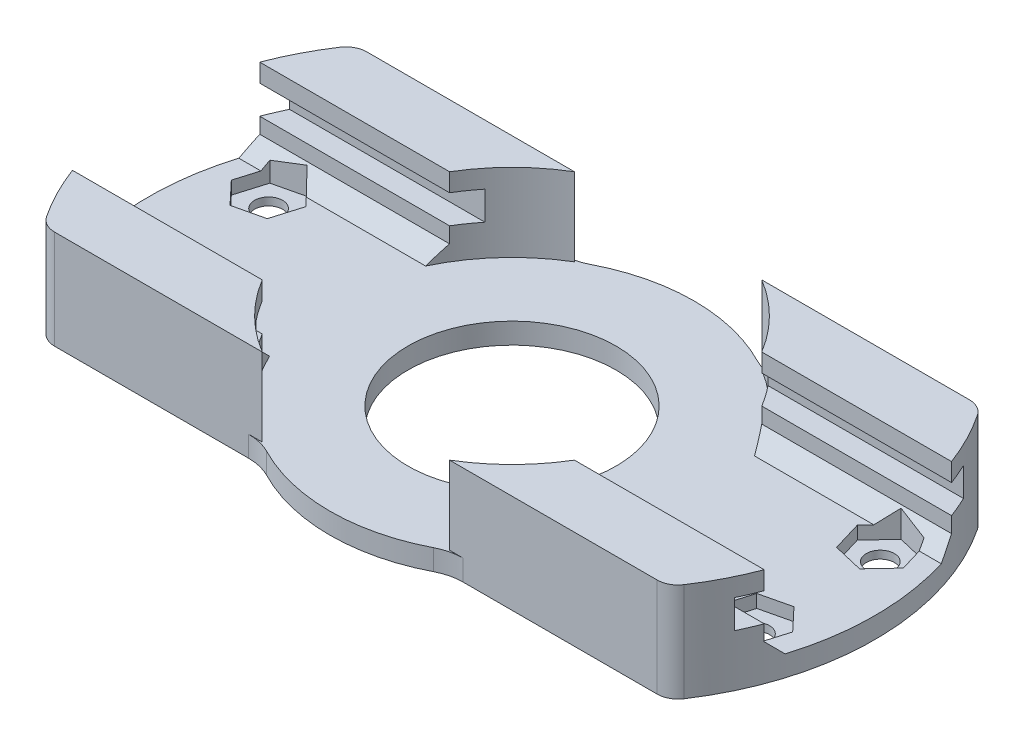
SolidWorks part; units mm, degrees
ref_plane "Спереди" through (0, 0, 0) normal (0, 0, 1) x (1, 0, 0)
ref_plane "Сверху" through (0, 0, 0) normal (0, 1, 0) x (1, 0, 0)
ref_plane "Справа" through (0, 0, 0) normal (1, 0, 0) x (0, 0, -1)
sketch "Эскиз1" plane through (0, 0, 0) normal (0, 1, 0) x (1, 0, 0)
  line L0 (-2.3838, 26) -> (62.3838, 26)
  line L1 (0, 0) -> (60, 0)
  line L2 (0, 0) -> (0, 30) construction
  line L3 (0, 30) -> (60, 30)
  line L4 (60, 0) -> (60, 30) construction
  line L5 (-4.8784, 15) -> (64.8784, 15) construction
  line L6 (-3.2374, 24) -> (63.2374, 24)
  line L7 (-2.3838, 4) -> (62.3838, 4)
  line L8 (-3.2374, 6) -> (63.2374, 6)
  line L9 (15, 0) -> (15, 6)
  line L10 (15, 30) -> (15, 24)
  line L11 (30, 30) -> (30, 0) construction
  line L12 (45, 0) -> (45, 6)
  line L13 (45, 30) -> (45, 24)
  arc A0 (0, 30) -> (0, 0) centre (20.6216, 15) ccw
  arc A1 (60, 30) -> (60, 0) centre (39.3784, 15) cw
  circle A2 centre (30, 15) radius 17.4929
  dimension "D3" = 25.5
  dimension "D1" = 60
  dimension "D2" = 30
  dimension "D4" = 4
  dimension "D5" = 2
  dimension "D6" = 15
extrude "Бобышка-Вытянуть1" add sketch "Эскиз1" along normal blind 2 contours A1 L1 A0 L3
extrude "Бобышка-Вытянуть2" add sketch "Эскиз1<3>" along normal blind 3 from surface contours L3 A0 L0 L10 | L0 A0 L6 L10 | L7 A0 L1 L9 | L8 A0 L7 L9 | A1 L3 L13 L0 | A1 L0 L13 L6 | A1 L8 L12 L7 | A1 L7 L12 L1 | A2 L1 L12 L7 | A2 L7 L12 | A2 L13 L0 | A2 L0 L13 L3 | A2 L0 L10 | A2 L3 L10 L0 | A2 L7 L9 L1 | A2 L9 L7 region at (6.8482, 0, -27.9513) region at (6.0846, 0, -24.992) region at (16.9656, 0, -28.4412) region at (15.4547, 0, -25.3502) region at (6.0846, 0, -5.008) region at (43.0344, 0, -28.4412) region at (44.5453, 0, -25.3502) region at (53.9154, 0, -24.992) region at (15.4547, 0, -4.6498) region at (6.8482, 0, -2.0487) region at (53.1518, 0, -27.9513) region at (53.9154, 0, -5.008) region at (44.5453, 0, -4.6498) region at (16.9656, 0, -1.5588) region at (43.0344, 0, -1.5588) region at (53.1518, 0, -2.0487) starting at face at (30, 2, -15)
sketch "Эскиз1<3>" plane through (0, 0, 0) normal (0, 1, 0) x (1, 0, 0) same geometry as "Эскиз1"
extrude "Бобышка-Вытянуть3" add sketch "Эскиз1<4>" along normal blind 2.75 from surface contours A1 L3 L13 L0 | A1 L7 L12 L1 | L7 A0 L1 L9 | L3 A0 L0 L10 | A2 L1 L12 L7 | A2 L7 L9 L1 | A2 L3 L10 L0 | A2 L0 L13 L3 region at (6.8482, 0, -27.9513) region at (16.9656, 0, -28.4412) region at (43.0344, 0, -28.4412) region at (6.8482, 0, -2.0487) region at (53.1518, 0, -27.9513) region at (16.9656, 0, -1.5588) region at (43.0344, 0, -1.5588) region at (53.1518, 0, -2.0487) starting at face at (8.048, 5, -27.1195)
sketch "Эскиз1<4>" plane through (0, 0, 0) normal (0, 1, 0) x (1, 0, 0) same geometry as "Эскиз1"
extrude "Бобышка-Вытянуть4" add sketch "Эскиз1<5>" along normal blind 1.75 from surface contours L3 A0 L0 L10 | L0 A0 L6 L10 | L8 A0 L7 L9 | L7 A0 L1 L9 | A1 L7 L12 L1 | A1 L8 L12 L7 | A1 L3 L13 L0 | A1 L0 L13 L6 | A2 L13 L0 | A2 L0 L13 L3 | A2 L1 L12 L7 | A2 L7 L12 | A2 L7 L9 L1 | A2 L9 L7 | A2 L3 L10 L0 | A2 L0 L10 region at (6.8482, 0, -27.9513) region at (6.0846, 0, -24.992) region at (16.9656, 0, -28.4412) region at (15.4547, 0, -25.3502) region at (6.0846, 0, -5.008) region at (43.0344, 0, -28.4412) region at (44.5453, 0, -25.3502) region at (53.9154, 0, -24.992) region at (15.4547, 0, -4.6498) region at (6.8482, 0, -2.0487) region at (53.1518, 0, -27.9513) region at (53.9154, 0, -5.008) region at (44.5453, 0, -4.6498) region at (16.9656, 0, -1.5588) region at (43.0344, 0, -1.5588) region at (53.1518, 0, -2.0487) starting at face at (51.3131, 7.75, -1.9359)
sketch "Эскиз1<5>" plane through (0, 0, 0) normal (0, 1, 0) x (1, 0, 0) same geometry as "Эскиз1"
sketch "Эскиз3" plane through (0, 0, 0) normal (0, 1, 0) x (1, 0, 0)
  line L0 (30, 0) -> (30, 30) construction
  line L1 (21, 0) -> (39, 0) construction
  line L2 (21, 30) -> (39, 30) construction
  circle A0 centre (30, 15) radius 10
  dimension "D1" = 20
extrude "Вырез-Вытянуть2" cut sketch "Эскиз3" along normal through all
fillet "Скругление3" [suppressed] radius 1
sketch "Эскиз7" plane through (0, 2, 0) normal (0, 1, 0) x (1, 0, 0)
  circle A0 centre (30, 15) radius 17.5
  circle A1 centre (30, 15) radius 10
  circle A2 centre (30, 15) radius 10 construction
  dimension "D1" = 35
extrude "Бобышка-Вытянуть5" add sketch "Эскиз7" against normal through all
fillet "Скругление2" [suppressed] radius 2
sketch "Эскиз8" plane through (0, 0, 0) normal (0, -1, 0) x (1, 0, 0)
  line L1 (0.6061, -21) -> (59.3939, -21) construction
  line L2 (0.6061, -21) -> (0.6061, -9) construction
  line L3 (0.6061, -9) -> (59.3939, -9) construction
  line L4 (59.3939, -21) -> (59.3939, -9) construction
  line L5 (0.6061, -21) -> (59.3939, -9) construction
  line L6 (0.6061, -9) -> (59.3939, -21) construction
  circle A0 centre (30, -15) radius 30 construction
  circle A1 centre (59.3939, -21) radius 1.35
  circle A2 centre (59.3939, -9) radius 1.35
  circle A3 centre (0.6061, -9) radius 1.35
  circle A4 centre (0.6061, -21) radius 1.35
  dimension "D1" = 60
  dimension "D2" = 2.7
  dimension "D3" = 12
extrude "Вырез-Вытянуть3" cut sketch "Эскиз8" against normal through all
sketch "Эскиз9" plane through (0, 2, 0) normal (0, 1, 0) x (1, 0, 0)
  line L0 (30, 30.5) -> (30, -2.5) construction
  line L1 (60.2477, 18.1519) -> (62.2873, 20.3153)
  line L2 (62.2873, 20.3153) -> (61.4335, 23.1635)
  line L3 (61.4335, 23.1635) -> (58.5401, 23.8481)
  line L4 (58.5401, 23.8481) -> (56.5004, 21.6847)
  line L5 (56.5004, 21.6847) -> (57.3542, 18.8365)
  line L6 (57.3542, 18.8365) -> (60.2477, 18.1519)
  line L7 (62.2873, 9.6847) -> (60.2477, 11.8481)
  line L8 (60.2477, 11.8481) -> (57.3542, 11.1635)
  line L9 (57.3542, 11.1635) -> (56.5004, 8.3153)
  line L10 (56.5004, 8.3153) -> (58.5401, 6.1519)
  line L11 (58.5401, 6.1519) -> (61.4335, 6.8365)
  line L12 (61.4335, 6.8365) -> (62.2873, 9.6847)
  line L13 (-1.4335, 6.8365) -> (-2.2873, 9.6847)
  line L14 (1.4599, 6.1519) -> (-1.4335, 6.8365)
  line L15 (3.4996, 8.3153) -> (1.4599, 6.1519)
  line L16 (2.6458, 11.1635) -> (3.4996, 8.3153)
  line L17 (-0.2477, 11.8481) -> (2.6458, 11.1635)
  line L18 (-2.2873, 9.6847) -> (-0.2477, 11.8481)
  line L19 (2.6458, 18.8365) -> (-0.2477, 18.1519)
  line L20 (3.4996, 21.6847) -> (2.6458, 18.8365)
  line L21 (1.4599, 23.8481) -> (3.4996, 21.6847)
  line L22 (-1.4335, 23.1635) -> (1.4599, 23.8481)
  line L23 (-2.2873, 20.3153) -> (-1.4335, 23.1635)
  line L24 (-0.2477, 18.1519) -> (-2.2873, 20.3153)
  line L25 (63.5843, 6.9433) -> (64.0247, 8.4124) construction
  line L26 (61.8604, 8.2606) -> (63.8045, 7.6778) construction
  circle A0 centre (59.3939, 21) radius 2.575 construction
  circle A1 centre (59.3939, 9) radius 2.575 construction
  circle A4 centre (0.6061, 9) radius 2.575 construction
  circle A5 centre (0.6061, 21) radius 2.575 construction
  arc A6 (63.2374, 6) -> (63.2374, 24) centre (39.3784, 15) ccw construction
  arc A7 (20.9861, 0) -> (39.0139, 0) centre (30, 15) ccw construction
  dimension "D1" = 5.15
extrude "Вырез-Вытянуть4" cut sketch "Эскиз9" against normal blind 1.25
fillet "Скругление5" [suppressed] radius 3
fillet "Скругление6" [suppressed] radius 2
chamfer "Фаска1" distance 1.5 angle 45 4 edges at (5.8813, 2, -6) (54.1187, 2, -6) (54.1187, 2, -24) (5.8813, 2, -24)
fillet "Скругление10" radius 2 4 edges at (60, 4.75, -30) (0, 4.75, -30) (60, 4.75, 0) (0, 4.75, 0)
fillet "Скругление11" radius 5 4 edges at (39.0139, 1, -30) (20.9861, 1, -30) (39.0139, 1, 0) (20.9861, 1, 0)
